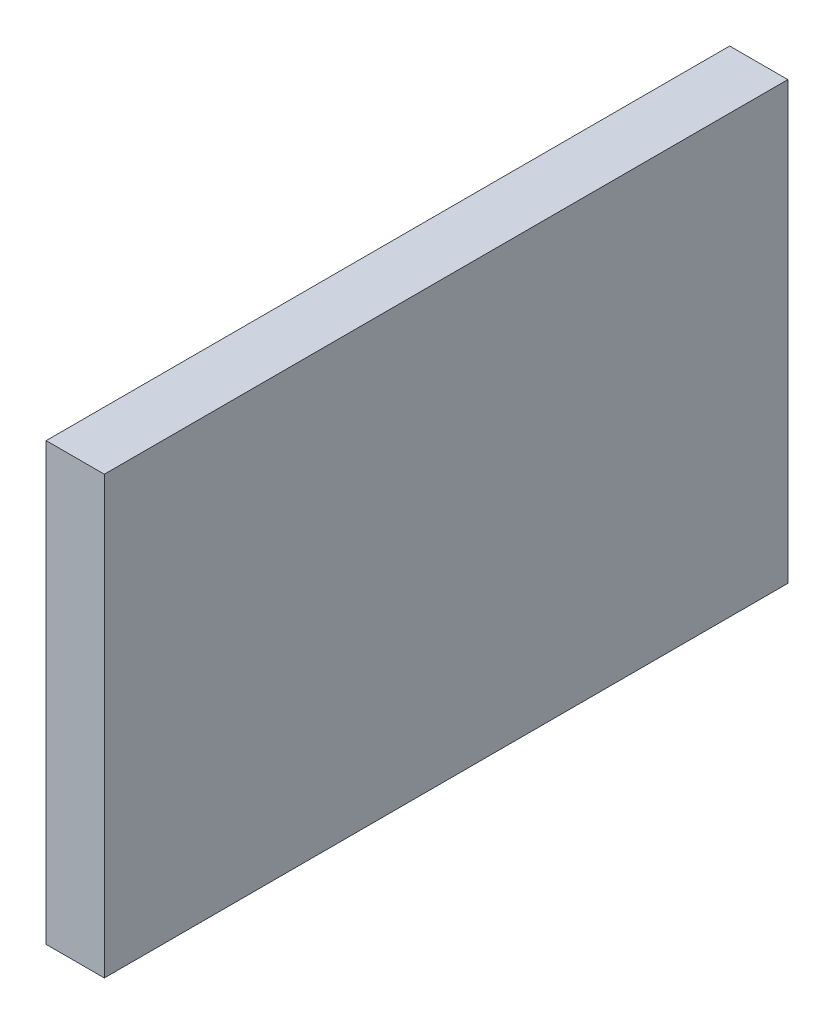
SolidWorks part; units mm, degrees
material "Acrylic (Medium-high impact)"
ref_plane "Front Plane" through (0, 0, 0) normal (0, 0, 1) x (1, 0, 0)
ref_plane "Top Plane" through (0, 0, 0) normal (0, 1, 0) x (1, 0, 0)
ref_plane "Right Plane" through (0, 0, 0) normal (1, 0, 0) x (0, 0, -1)
sketch "Sketch1" plane through (0, 0, 74.5305) normal (0, 0, -1) x (-1, 0, 0)
  line L0 (-51.9215, 24.6718) -> (-56.9215, 24.6718) construction
  line L1 (-56.9215, 47.1718) -> (-53.9215, 47.1718)
  line L2 (-56.9215, 47.1718) -> (-56.9215, 24.6718)
  line L3 (-56.9215, 24.6718) -> (-53.9215, 24.6718)
  line L4 (-53.9215, 47.1718) -> (-53.9215, 24.6718)
  dimension "D1" = 3
extrude "Boss-Extrude1" add sketch "Sketch1" along normal up to surface (35.25 mm away)
